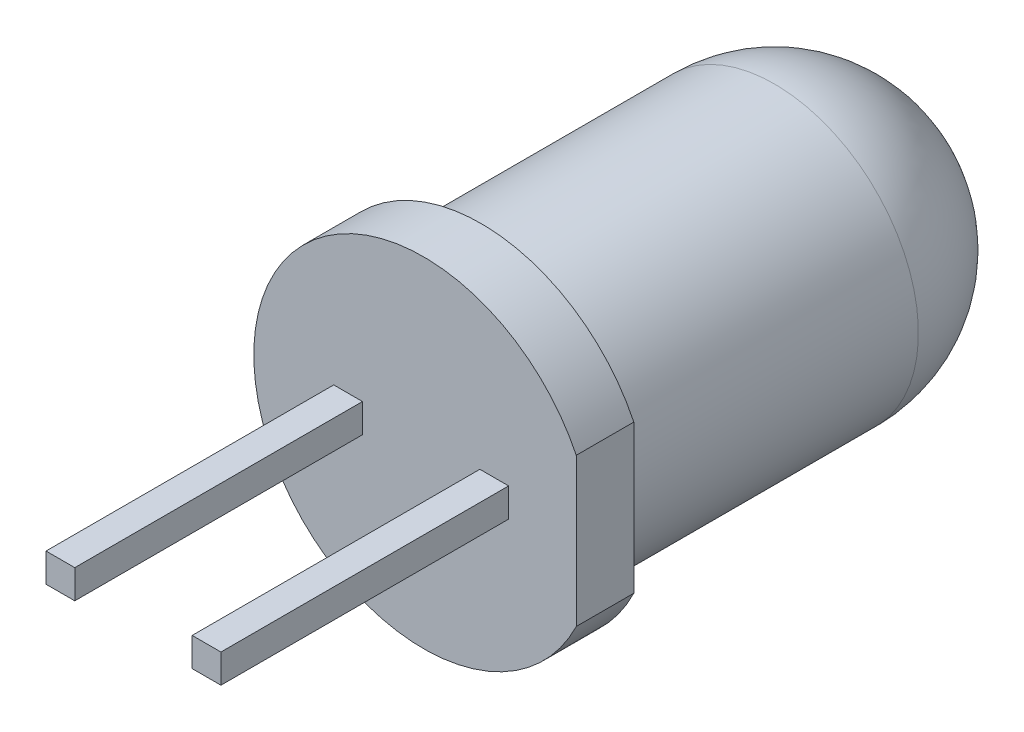
SolidWorks part; units mm, degrees
ref_plane "Front Plane" through (0, 0, 0) normal (0, 0, 1) x (1, 0, 0)
ref_plane "Top Plane" through (0, 0, 0) normal (0, 1, 0) x (1, 0, 0)
ref_plane "Right Plane" through (0, 0, 0) normal (1, 0, 0) x (0, 0, -1)
sketch "Sketch1" plane through (0, 0, 0) normal (0, 1, 0) x (1, 0, 0)
  line L0 (0.0414, -1.3187) -> (-2.9086, -1.3187)
  line L1 (-2.9086, -1.3187) -> (-2.9086, -0.3187)
  line L2 (-2.9086, -0.3187) -> (-2.4586, -0.3187)
  line L3 (-2.4586, -0.3187) -> (-2.4586, 4.7813)
  line L4 (0.0414, 7.2813) -> (0.0414, -1.3187) construction
  line L5 (0.0414, 7.2813) -> (-4.1738, 7.2812) construction
  line L6 (-0.2586, 6.9607) -> (0.0414, 6.9607)
  line L7 (-0.2586, -1.0187) -> (0.0414, -1.0187)
  line L8 (-0.2586, -1.0187) -> (-2.6086, -1.0187)
  line L9 (-2.6086, -1.0187) -> (-2.6086, -0.6187)
  line L10 (-2.6086, -0.6187) -> (-2.1586, -0.6187)
  line L11 (-2.1586, -0.6187) -> (-2.1586, 4.7813)
  line L12 (-0.2586, 6.9607) -> (-0.2586, -1.0187) construction
  line L13 (0.0414, 7.2813) -> (0.0414, -1.3187) construction
  line L14 (0.0414, 7.2813) -> (0.0414, 6.9607)
  line L15 (0.0414, -1.0187) -> (0.0414, -1.3187)
  line L16 (0.0414, -1.3187) -> (0.04, -1.314)
  arc A0 (-2.4586, 4.7813) -> (0.0414, 7.2813) centre (0.0414, 4.7813) cw
  arc A1 (-2.1586, 4.7813) -> (-0.2586, 6.9607) centre (0.0414, 4.7813) cw
  dimension "D1" = 8.6
  dimension "D2" = 2.5
  dimension "D3" = 2.95
  dimension "D4" = 1
  dimension "D5" = 0.3
revolve "Revolve3" add sketch "Sketch1" angle 360 about L4 region at (-1.4336, 0, 1.2278)
sketch "Sketch2" plane through (0, 0, 1.3187) normal (0, 0, 1) x (1, 0, 0)
  line L0 (1.52, 0.2398) -> (1.02, 0.2398)
  line L1 (-1.02, 0.2398) -> (-1.52, 0.2398)
  line L2 (-1.02, 0.2398) -> (-1.02, -0.2602)
  line L3 (-1.02, -0.2602) -> (-1.52, -0.2602)
  line L4 (-1.52, 0.2398) -> (-1.52, -0.2602)
  line L5 (1.52, 0.2398) -> (1.52, -0.2602)
  line L6 (1.52, -0.2602) -> (1.02, -0.2602)
  line L7 (1.02, 0.2398) -> (1.02, -0.2602)
  point P4 (-1.27, 0.2398)
  point P5 (1.27, 0.2398)
  point P10 (1.27, -0.2602)
  dimension "D1" = 0.5
  dimension "D2" = 0.5
  dimension "D4" = 2.54
  dimension "D5" = 1.27
  dimension "D3" = 2
extrude "Boss-Extrude1" add sketch "Sketch2" along normal blind 5
sketch "Sketch3" plane through (0.0201, 0, 1.3187) normal (0, 0, 1) x (1, 0, 0)
  line L0 (2.6752, 2.1927) -> (2.6752, -2.2689)
  line L1 (2.6752, -2.2689) -> (4.2948, -2.5024)
  line L2 (4.2948, -2.5024) -> (4.1605, 2.2994)
  line L3 (4.1605, 2.2994) -> (2.6752, 2.1927)
extrude "Cut-Extrude1" cut sketch "Sketch3" against normal up to next
